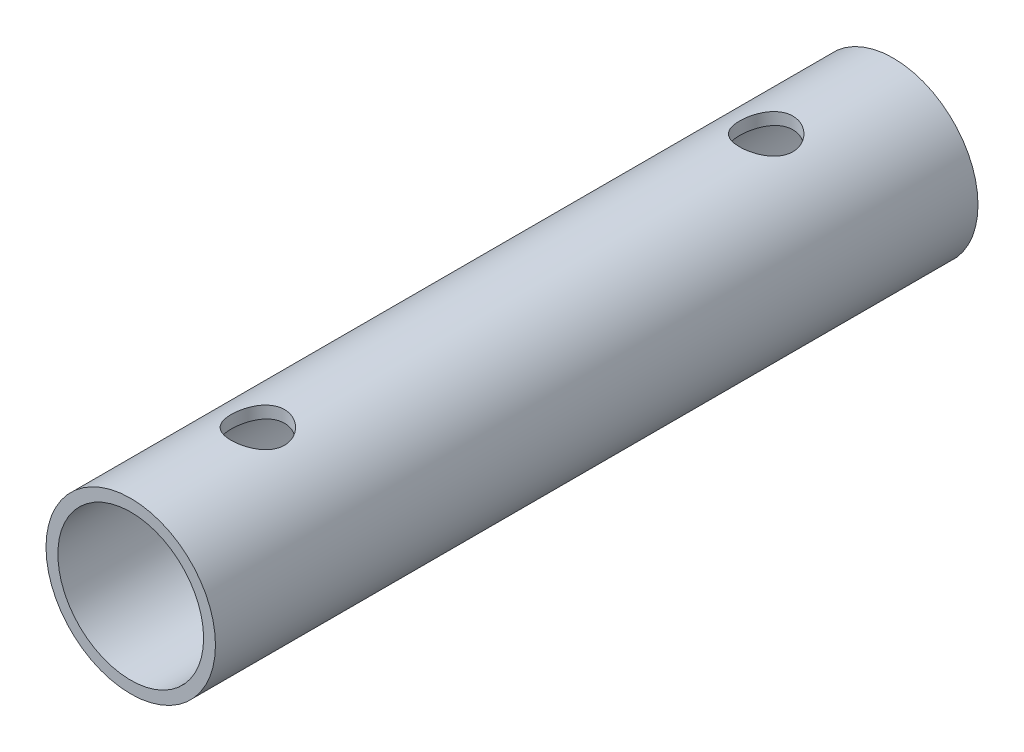
SolidWorks part; units mm, degrees
ref_plane "Front" through (0, 0, 0) normal (0, 0, 1) x (1, 0, 0)
ref_plane "Top" through (0, 0, 0) normal (0, 1, 0) x (1, 0, 0)
ref_plane "Right" through (0, 0, 0) normal (1, 0, 0) x (0, 0, -1)
sketch "Sketch1" plane through (0, 0, 0) normal (0, 0, 1) x (1, 0, 0)
  circle A0 centre (0, 0) radius 6.35
  circle A1 centre (0, 0) radius 5.461
extrude "Extrude1" add sketch "Sketch1" along normal blind 57.15
sketch "Sketch2" plane through (0, 0, 0) normal (0, 1, 0) x (1, 0, 0)
  line L0 (0, 0) -> (0, -9.525)
  line L2 (-6.35, -57.15) -> (6.35, -57.15) construction
  line L3 (0, -57.15) -> (0, -47.625)
  circle A0 centre (0, -9.525) radius 2
  circle A1 centre (0, -47.625) radius 2
extrude "Cut-Extrude1" cut sketch "Sketch2" against normal blind 38.1 and the other way blind 38.1
ref_axis "Axis1" through (0, 0, 57.15) along (0, 0, -1)
